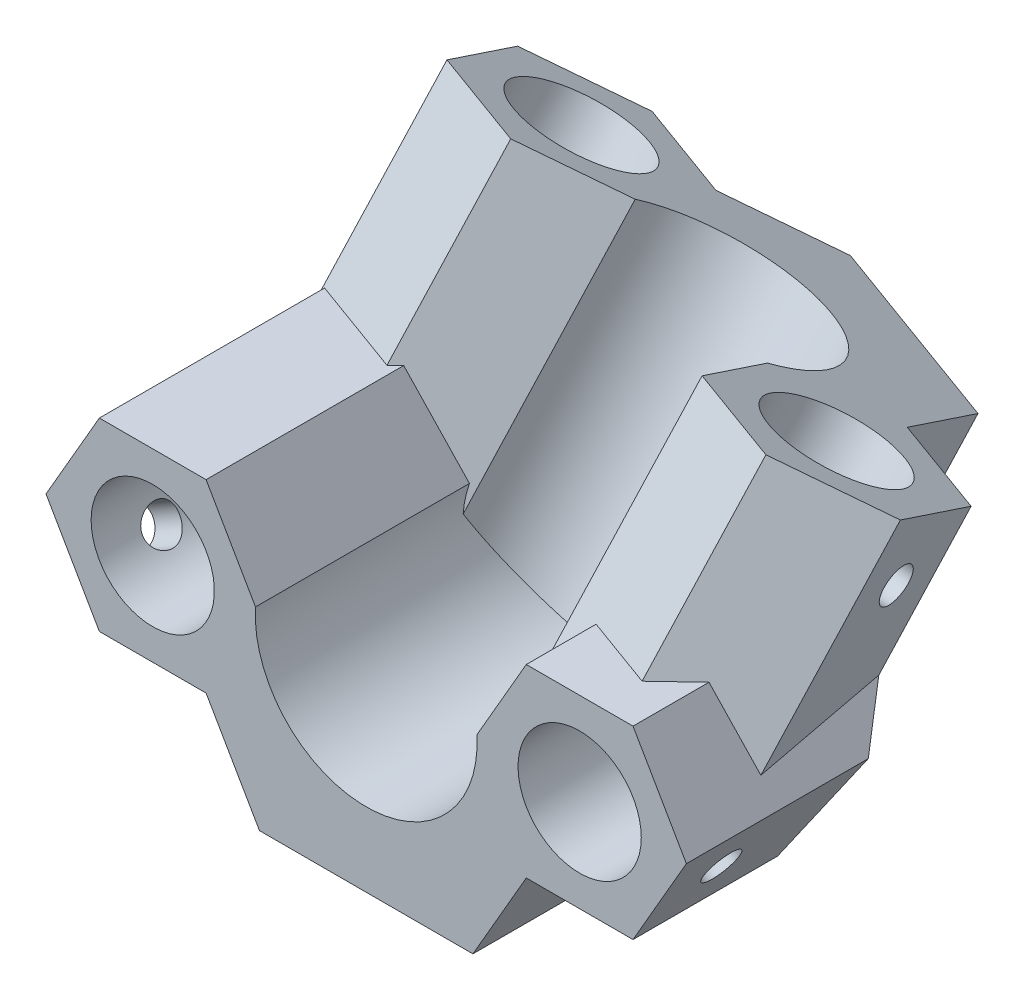
SolidWorks part; units mm, degrees
ref_plane "Front Plane" through (0, 0, 0) normal (0, 0, 1) x (1, 0, 0)
ref_plane "Top Plane" through (0, 0, 0) normal (0, 1, 0) x (1, 0, 0)
ref_plane "Right Plane" through (0, 0, 0) normal (1, 0, 0) x (0, 0, -1)
sketch "Sketch2" plane through (0, 0, 0) normal (0, 1, 0) x (1, 0, 0)
  line L0 (0, 0) -> (0, -10) construction
  line L1 (0, 0) -> (3.4202, 9.3969) construction
  dimension "D1" = 10
  dimension "D2" = 10
  dimension "D3" = 160
ref_plane "Plane1" through (0, 0, 0) normal (0.9397, 0, 0.342) x (0.342, 0, -0.9397)
sketch "Sketch3" plane through (0, 0, 0) normal (0.9397, 0, 0.342) x (0.342, 0, -0.9397)
  line L0 (0, 0) -> (10, 17.3205) construction
  line L1 (10, 17.3205) -> (10, 0) construction
  line L2 (10, 0) -> (0, 0) construction
  dimension "D1" = 30
  dimension "D2" = 10
sketch "Sketch5" plane through (0, 0, 0) normal (0, 0, 1) x (1, 0, 0)
  line L0 (0, 0) -> (8.6603, 0) construction
  line L1 (14.8205, 4.3301) -> (8.6603, 15)
  line L2 (8.6603, 15) -> (-8.6603, 15)
  line L3 (-8.6603, 15) -> (-12.9904, 7.5)
  line L4 (-12.9904, -7.5) -> (-8.6603, -15)
  line L5 (-8.6603, -15) -> (8.6603, -15)
  line L6 (8.6603, -15) -> (12.9904, -7.5)
  line L7 (0, -13.4183) -> (0, 13.4183) construction
  line L8 (25.9808, 0) -> (21.6506, 7.5)
  line L9 (21.6506, 7.5) -> (12.9904, 7.5)
  line L10 (12.9904, 7.5) -> (8.9827, 0.5584)
  line L11 (8.6603, 0) -> (8.9827, -0.5584) construction
  line L12 (12.9904, -7.5) -> (21.6506, -7.5)
  line L13 (21.6506, -7.5) -> (25.9808, 0)
  line L14 (-21.6506, -7.5) -> (-25.9808, 0)
  line L15 (-12.9904, -7.5) -> (-21.6506, -7.5)
  line L16 (-8.9827, -0.5584) -> (-12.9904, -7.5) construction
  line L17 (-12.9904, 7.5) -> (-8.9827, 0.5584)
  line L18 (-21.6506, 7.5) -> (-12.9904, 7.5)
  line L19 (-25.9808, 0) -> (-21.6506, 7.5)
  line L20 (-12.9904, 7.5) -> (-14.8205, 4.3301) construction
  line L21 (-14.8205, 4.3301) -> (-17.3205, 0) construction
  line L22 (-17.3205, 0) -> (-14.8205, -4.3301) construction
  line L23 (-14.8205, -4.3301) -> (-12.9904, -7.5) construction
  line L24 (-8.9827, 0.5584) -> (-8.6603, 0) construction
  line L25 (-8.6603, 0) -> (-8.9827, -0.5584) construction
  line L26 (10.8253, -3.75) -> (12.9904, -7.5) construction
  line L27 (12.9904, -7.5) -> (13.5705, -6.4952) construction
  line L28 (14.8205, -4.3301) -> (17.3205, 0) construction
  line L29 (13.5705, -6.4952) -> (14.8205, -4.3301) construction
  line L30 (8.9827, -0.5584) -> (10.8253, -3.75) construction
  line L31 (8.9827, 0.5584) -> (8.6603, 0) construction
  line L32 (8.6603, 0) -> (9, 0) construction
  line L33 (9, 0) -> (15, 0) construction
  line L34 (15, 0) -> (17.3205, 0) construction
  line L35 (17.3205, 0) -> (14.8205, 4.3301) construction
  circle A0 centre (0, 0) radius 15 construction
  arc A1 (-8.9827, 0.5584) -> (8.9827, 0.5584) centre (0, 0) ccw
  circle A2 centre (17.3205, 0) radius 7.5 construction
  circle A3 centre (17.3205, 0) radius 5
  circle A4 centre (-17.3205, 0) radius 5
  arc A5 (8.9827, 0.5584) -> (-8.9827, 0.5584) centre (0, 0) ccw construction
  dimension "D2" = 18
  dimension "D4" = 10
  dimension "D1" = 30
  dimension "D3" = 15
extrude "Boss-Extrude2" add sketch "Sketch5" along normal blind 15 contours A4 | L17 A1 L10 L9 L8 L13 L12 L6 L5 L4 L15 L14 L19 L18 | A3
ref_plane "Plane2" through (3.4202, 17.3205, -9.3969) normal (0.171, 0.866, -0.4698) x (0.9853, -0.1503, 0.0815)
sketch "Sketch10" plane through (0, 0, 0) normal (0, 0, -1) x (-1, 0, 0)
  line L0 (-8.9827, 0.5584) -> (-12.9904, 7.5)
  line L1 (-12.9904, 7.5) -> (-21.6506, 7.5)
  line L2 (-21.6506, 7.5) -> (-25.9808, 0)
  line L3 (-25.9808, 0) -> (-21.6506, -7.5)
  line L4 (-21.6506, -7.5) -> (-12.9904, -7.5)
  line L5 (-12.9904, -7.5) -> (-8.6603, -15)
  line L6 (-8.6603, -15) -> (8.6603, -15)
  line L7 (8.6603, -15) -> (12.9904, -7.5)
  line L8 (12.9904, -7.5) -> (21.6506, -7.5)
  line L9 (21.6506, -7.5) -> (25.9808, 0)
  line L10 (25.9808, 0) -> (21.6506, 7.5)
  line L11 (21.6506, 7.5) -> (12.9904, 7.5)
  line L12 (21.6506, 7.5) -> (12.9904, 7.5) construction
  line L13 (12.9904, 7.5) -> (8.9827, 0.5584)
  arc A0 (-8.9827, 0.5584) -> (8.9827, 0.5584) centre (0, 0) ccw
  arc A1 (-8.9827, 0.5584) -> (8.9827, 0.5584) centre (0, 0) ccw construction
  arc A2 (8.9827, 0.5584) -> (-8.9827, 0.5584) centre (0, 0) ccw construction
sketch "Sketch6" plane through (3.4202, 17.3205, -9.3969) normal (0.171, 0.866, -0.4698) x (0.9853, -0.1503, 0.0815)
  line L0 (-4.5094, -14.3061) -> (4.5094, 14.3061) construction
  line L1 (-3.7502, 16.9096) -> (-10.1348, 11.0583)
  line L2 (-15.4367, 0.3256) -> (-14.6442, -3.2478)
  line L3 (-12.769, -11.7026) -> (-4.5094, -14.3061) construction
  line L4 (10.1348, -11.0583) -> (10.9901, -10.2744) construction
  line L5 (14.6442, 3.2478) -> (12.769, 11.7026)
  line L6 (12.769, 11.7026) -> (-3.7502, 16.9096)
  line L7 (2.6035, 8.2596) -> (0, 0) construction
  line L8 (-14.3061, 4.5094) -> (16.5193, -5.207) construction
  line L9 (3.7502, -16.9096) -> (10.1348, -11.0583) construction
  line L10 (24.7789, -7.8105) -> (22.9038, 0.6443)
  line L11 (22.9038, 0.6443) -> (14.6442, 3.2478)
  line L12 (14.6442, 3.2478) -> (11.4519, 0.3222) construction
  line L13 (8.3993, -3.233) -> (10.1348, -11.0583)
  line L14 (10.1348, -11.0583) -> (18.3944, -13.6618)
  line L15 (18.3944, -13.6618) -> (24.7789, -7.8105)
  line L16 (-24.7789, 7.8105) -> (-22.9038, -0.6443)
  line L17 (-22.9038, -0.6443) -> (-14.6442, -3.2478)
  line L18 (-14.6442, -3.2478) -> (-8.735, 2.1678)
  line L19 (-9.1972, 6.8309) -> (-10.1348, 11.0583) construction
  line L20 (-10.1348, 11.0583) -> (-18.3944, 13.6618)
  line L21 (-18.3944, 13.6618) -> (-24.7789, 7.8105)
  line L22 (-4.5094, -14.3061) -> (3.7502, -16.9096) construction
  line L23 (-14.6442, -3.2478) -> (-12.769, -11.7026) construction
  line L24 (-8.735, 2.1678) -> (-8.2596, 2.6035) construction
  line L25 (-8.2596, 2.6035) -> (-8.3993, 3.233) construction
  line L26 (-8.3993, 3.233) -> (-9.1972, 6.8309) construction
  line L27 (-10.1348, 11.0583) -> (-10.9901, 10.2744) construction
  line L28 (-12.8332, 8.5853) -> (-16.5193, 5.207) construction
  line L29 (-10.9901, 10.2744) -> (-12.8332, 8.5853) construction
  line L30 (-16.5193, 5.207) -> (-14.3061, 4.5094) construction
  line L31 (-16.5193, 5.207) -> (-15.4367, 0.3256) construction
  line L32 (8.2596, -2.6035) -> (8.3993, -3.233) construction
  line L33 (8.735, -2.1678) -> (8.2596, -2.6035) construction
  line L34 (11.4519, 0.3222) -> (8.735, -2.1678) construction
  line L35 (16.5193, -5.207) -> (15.4367, -0.3256) construction
  line L36 (15.4367, -0.3256) -> (14.8954, 2.1151) construction
  line L37 (14.8954, 2.1151) -> (14.6442, 3.2478) construction
  line L38 (12.8332, -8.5853) -> (16.5193, -5.207) construction
  line L39 (10.9901, -10.2744) -> (12.8332, -8.5853) construction
  circle A0 centre (0, 0) radius 15 construction
  arc A1 (8.3993, -3.233) -> (-8.735, 2.1678) centre (0, 0) ccw
  circle A2 centre (16.5193, -5.207) radius 7.5 construction
  circle A3 centre (16.5193, -5.207) radius 5
  circle A4 centre (-16.5193, 5.207) radius 7.5 construction
  circle A5 centre (-16.5193, 5.207) radius 5
  arc A6 (-2.7056, -8.5837) -> (8.3993, -3.233) centre (0, 0) ccw construction
  arc A7 (-8.735, 2.1678) -> (-2.7056, -8.5837) centre (0, 0) ccw construction
  dimension "D2" = 18
  dimension "D3" = 10
  dimension "D5" = 10
  dimension "D1" = 30
  dimension "D4" = 15
  dimension "D6" = 15
extrude "Boss-Extrude3" add sketch "Sketch6" against normal up to surface (37.3205 mm away) contours L18 A1 L13 L14 L15 L10 L11 L5 L6 L1 L20 L21 L16 L17 | A5 | A3 up to face at (0, -15, 7.5)
sketch "Sketch7" plane through (0, 0, 15) normal (0, 0, 1) x (1, 0, 0)
  circle A0 centre (-17.3205, 0) radius 5
  circle A1 centre (-17.3205, 0) radius 5 construction
  circle A2 centre (0, 0) radius 9
  arc A3 (-8.9827, 0.5584) -> (8.9827, 0.5584) centre (0, 0) ccw construction
  circle A4 centre (17.3205, 0) radius 5
  arc A5 (19.6231, -4.4382) -> (12.6933, -1.8945) centre (17.3205, 0) ccw construction
extrude "Cut-Extrude1" cut sketch "Sketch7" against normal up to surface (15 mm away) up to face at (-13.56, -1.3492, 0)
sketch "Sketch8" plane through (0, 0, 0) normal (0, 1, 0) x (1, 0, 0)
  line L0 (-25.9808, -15) -> (25.9808, -15)
  line L1 (25.9808, -15) -> (25.9808, -23.6809)
  line L2 (25.9808, -23.6809) -> (-25.9808, -23.6809)
  line L3 (-25.9808, -23.6809) -> (-25.9808, -15)
extrude "Cut-Extrude2" cut sketch "Sketch8" against normal through all both and the other way through all
sketch "Sketch9" plane through (0, 0, 15) normal (0, 0, 1) x (1, 0, 0)
  line L0 (-8.6603, -15) -> (-12.9904, -7.5)
  line L1 (-12.9904, -7.5) -> (-21.6506, -7.5)
  line L2 (-21.6506, -7.5) -> (-25.9808, 0)
  line L3 (-25.9808, 0) -> (-27.3759, -15)
  line L4 (-27.3759, -15) -> (-8.6603, -15)
  line L5 (8.6603, -15) -> (12.9904, -7.5)
  line L6 (12.9904, -7.5) -> (21.6506, -7.5)
  line L7 (21.6506, -7.5) -> (25.9808, 0)
  line L8 (25.9808, 0) -> (21.219, -15)
  line L9 (21.219, -15) -> (8.6603, -15)
extrude "Cut-Extrude3" cut sketch "Sketch9" against normal through all both and the other way through all
extrude "Boss-Extrude4" add sketch "Sketch10" along normal up to surface (15.5058 mm away) up to face at (6.3157, -3.7874, -13.8064)
sketch "Sketch11" plane through (3.4202, 17.3205, -9.3969) normal (0.171, 0.866, -0.4698) x (0.9853, -0.1503, 0.0815)
  line L0 (-3.7502, 16.9096) -> (-10.1348, 11.0583)
  line L1 (-10.1348, 11.0583) -> (-18.3944, 13.6618)
  line L2 (-18.3944, 13.6618) -> (-26.2017, 6.5066)
  line L3 (-24.3748, -13.1846) -> (-27.8723, 24.5131) construction
  line L4 (-26.2017, 6.5066) -> (-27.8723, 24.5131)
  line L5 (-27.8723, 24.5131) -> (-3.7502, 16.9096)
  line L6 (12.769, 11.7026) -> (14.6442, 3.2478)
  line L7 (14.6442, 3.2478) -> (25.6176, -0.2111)
  line L8 (26.8213, -13.1846) -> (24.8661, 7.8896) construction
  line L9 (25.6176, -0.2111) -> (24.8661, 7.8896)
  line L10 (24.8661, 7.8896) -> (12.769, 11.7026)
extrude "Cut-Extrude4" cut sketch "Sketch11" against normal through all both and the other way through all
sketch "Sketch12" plane through (-19.4856, -11.25, 0) normal (-0.866, -0.5, 0) x (0, 0, 1)
  line L0 (15, 8.6603) -> (-8.119, 8.6603) construction
  line L1 (15, 4.3301) -> (15, 12.9904) construction
  line L2 (-8.8355, 4.3301) -> (-7.4025, 12.9904) construction
  circle A0 centre (10, 8.6603) radius 1.5
  dimension "D1" = 3
  dimension "D2" = 5
extrude "Cut-Extrude5" cut sketch "Sketch12" against normal up to surface and the other way through all up to face at (-22.3205, 0, 15)
sketch "Sketch13" plane through (19.4856, -11.25, 0) normal (0.866, -0.5, 0) x (0, 0, -1)
  line L0 (-15, 8.6603) -> (-1.7562, 8.6603) construction
  line L1 (-15, 4.3301) -> (-15, 12.9904) construction
  line L2 (-3.2722, 4.3301) -> (-0.2402, 12.9904) construction
  circle A0 centre (-10, 8.6603) radius 1.5
  dimension "D1" = 3
  dimension "D2" = 5
extrude "Cut-Extrude6" cut sketch "Sketch13" against normal up to surface (2.7303 mm away) contours A0 up to face at (17.3205, 0, 0.3293)
sketch "Sketch14" plane through (21.6427, -5.625, -2.4908) normal (0.9619, -0.25, -0.1107) x (-0.1071, 0.0278, -0.9939)
  line L0 (1.8237, 21.7181) -> (-5.114, 8.7865) construction
  line L1 (-1.992, 23.7651) -> (5.6394, 19.671) construction
  line L2 (0.1152, 9.3741) -> (-10.3432, 8.1988) construction
  circle A0 centre (-0.5401, 17.3121) radius 1.5
  dimension "D1" = 3
  dimension "D2" = 5
extrude "Cut-Extrude7" cut sketch "Sketch14" against normal up to surface (2.5505 mm away) up to face at (19.6962, 19.7049, 0.9219)
sketch "Sketch15" plane through (-14.9782, -5.625, -15.8197) normal (-0.6657, -0.25, -0.7031) x (-0.7462, 0.223, 0.6272)
  line L0 (3.8464, 21.4524) -> (9.6694, -3.2805) construction
  line L1 (-0.3685, 20.4601) -> (8.0613, 22.4447) construction
  line L2 (8.9416, -4.1065) -> (14.7444, 2.48) construction
  circle A0 centre (4.9923, 16.5855) radius 1.5
  dimension "D1" = 3
  dimension "D2" = 5
extrude "Cut-Extrude8" cut sketch "Sketch15" against normal up to surface (2.6834 mm away) contours A0 up to face at (-12.8558, 19.7049, -10.926)
